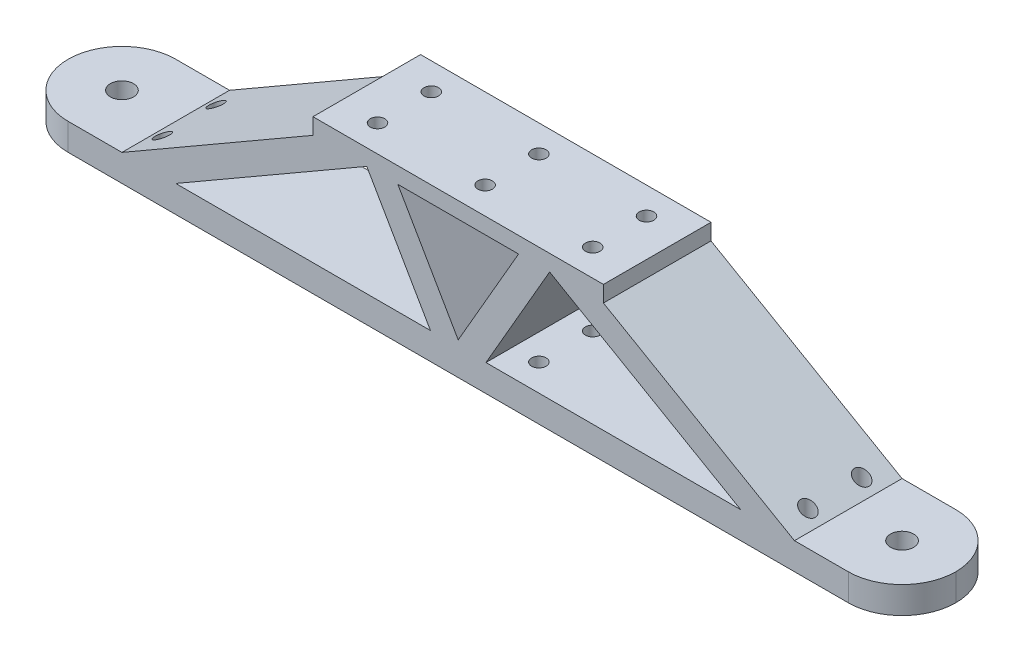
SolidWorks part; units mm, degrees
ref_plane "정면" through (0, 0, 0) normal (0, 0, 1) x (1, 0, 0)
ref_plane "윗면" through (0, 0, 0) normal (0, 1, 0) x (1, 0, 0)
ref_plane "우측면" through (0, 0, 0) normal (1, 0, 0) x (0, 0, -1)
sketch "스케치1" plane through (0, 0, 0) normal (0, 0, 1) x (1, 0, 0)
  line L0 (-31.993, 23) -> (-67.5, 2.5)
  line L1 (-87.5, 2.5) -> (-67.5, 2.5)
  line L2 (-87.5, 2.5) -> (-87.5, -2.5)
  line L3 (-87.5, -2.5) -> (77.5, -2.5)
  line L4 (77.5, 2.5) -> (77.5, -2.5)
  line L5 (0.1573, 2.5) -> (47.5, 2.5)
  line L11 (-31.993, 26) -> (21.993, 26)
  line L12 (-31.993, 26) -> (-31.993, 23)
  line L13 (-16.2195, 23) -> (6.2195, 23)
  line L14 (21.993, 26) -> (21.993, 23)
  line L15 (-31.993, 26) -> (0, 24.5) construction
  line L16 (0, 24.5) -> (21.993, 26) construction
  line L17 (21.993, 23) -> (57.5, 2.5)
  line L18 (-21.993, 23) -> (-57.5, 2.5)
  line L19 (11.993, 23) -> (47.5, 2.5)
  line L20 (-29.493, 18.6699) -> (-65, -1.8301) construction
  line L21 (19.493, 18.6699) -> (55, -1.8301) construction
  line L22 (-21.993, 23) -> (-10.1573, 2.5)
  line L23 (11.993, 23) -> (0.1573, 2.5)
  line L24 (57.5, 2.5) -> (77.5, 2.5)
  line L25 (-57.5, 2.5) -> (-10.1573, 2.5)
  line L28 (-16.2195, 23) -> (-5, 3.5673)
  line L29 (6.2195, 23) -> (-5, 3.5673)
  point P0 (0, 0)
  point P6 (0, 24.5)
  dimension "D1" = 165
  dimension "D2" = 5
  dimension "D3" = 3
  dimension "D4" = 30
  dimension "D5" = 20.5
  dimension "D6" = 20
  dimension "D7" = 20
  dimension "D8" = 30
  dimension "D9" = 5
  dimension "D11" = 5
  dimension "D10" = 5
extrude "보스-돌출1" add sketch "스케치1" along normal blind 20
sketch "스케치2" plane through (0, 2.5, 0) normal (0, 1, 0) x (1, 0, 0)
  line L0 (-87.5, -20) -> (-87.5, 0) construction
  line L1 (77.5, -20) -> (77.5, 0) construction
  circle A0 centre (-77.5, -10) radius 2.15
  circle A1 centre (67.5, -10) radius 2.15
  dimension "D1" = 4.3
  dimension "4.3" = 4.3
  dimension "D3" = 10
  dimension "D4" = 10
extrude "컷-돌출1" cut sketch "스케치2" against normal blind 20
sketch "스케치3" plane through (0, 26, 0) normal (0, 1, 0) x (1, 0, 0)
  line L0 (-5, 0) -> (-5, -20) construction
  line L1 (-25, -5) -> (15, -5) construction
  line L2 (-25, -5) -> (-25, -15) construction
  line L3 (-25, -15) -> (15, -15) construction
  line L4 (15, -5) -> (15, -15) construction
  line L5 (-25, -5) -> (15, -15) construction
  line L6 (-25, -15) -> (15, -5) construction
  line L7 (21.993, 0) -> (-31.993, 0) construction
  line L8 (21.993, -20) -> (-31.993, -20) construction
  line L9 (-31.993, -10) -> (21.993, -10) construction
  line L10 (-31.993, -20) -> (-31.993, 0) construction
  line L11 (21.993, -20) -> (21.993, 0) construction
  circle A0 centre (-25, -5) radius 1.35
  circle A1 centre (-25, -15) radius 1.35
  circle A2 centre (-5, -5) radius 1.35
  circle A3 centre (-5, -15) radius 1.35
  circle A4 centre (15, -5) radius 1.35
  circle A5 centre (15, -15) radius 1.35
  point P0 (-5, -10)
  dimension "D3" = 2.7
  dimension "D1" = 40
  dimension "D2" = 10
extrude "컷-돌출2" cut sketch "스케치3" against normal blind 10
fillet "필렛1" radius 10 4 edges at (77.5, 0, 0) (77.5, 0, 20) (-87.5, 0, 0) (-87.5, 0, 20)
sketch "스케치4" plane through (0, -2.5, 0) normal (0, -1, 0) x (1, 0, 0)
  line L0 (-5, 20) -> (-5, 0) construction
  line L1 (-65, 15) -> (55, 15) construction
  line L2 (-65, 15) -> (-65, 5) construction
  line L3 (-65, 5) -> (55, 5) construction
  line L4 (55, 15) -> (55, 5) construction
  line L5 (-65, 15) -> (55, 5) construction
  line L6 (-65, 5) -> (55, 15) construction
  line L7 (-77.5, 20) -> (67.5, 20) construction
  line L8 (-77.5, 0) -> (67.5, 0) construction
  line L9 (77.5, 10) -> (-87.5, 10) construction
  line L11 (-15, 5) -> (5, 5) construction
  line L12 (-15, 5) -> (-15, 15) construction
  line L13 (-15, 15) -> (5, 15) construction
  line L14 (5, 5) -> (5, 15) construction
  line L15 (-15, 5) -> (5, 15) construction
  line L16 (-15, 15) -> (5, 5) construction
  circle A0 centre (-65, 15) radius 1.35
  circle A1 centre (-65, 5) radius 1.35
  circle A2 centre (55, 5) radius 1.35
  circle A3 centre (55, 15) radius 1.35
  circle A6 centre (-15, 15) radius 1.35
  circle A7 centre (5, 15) radius 1.35
  circle A8 centre (-15, 5) radius 1.35
  circle A9 centre (5, 5) radius 1.35
  point P0 (-5, 10)
  point P19 (-5, 10)
  dimension "D3" = 20
  dimension "D4" = 2.7
  dimension "D1" = 120
  dimension "D2" = 10
extrude "컷-돌출3" cut sketch "스케치4" against normal blind 10
